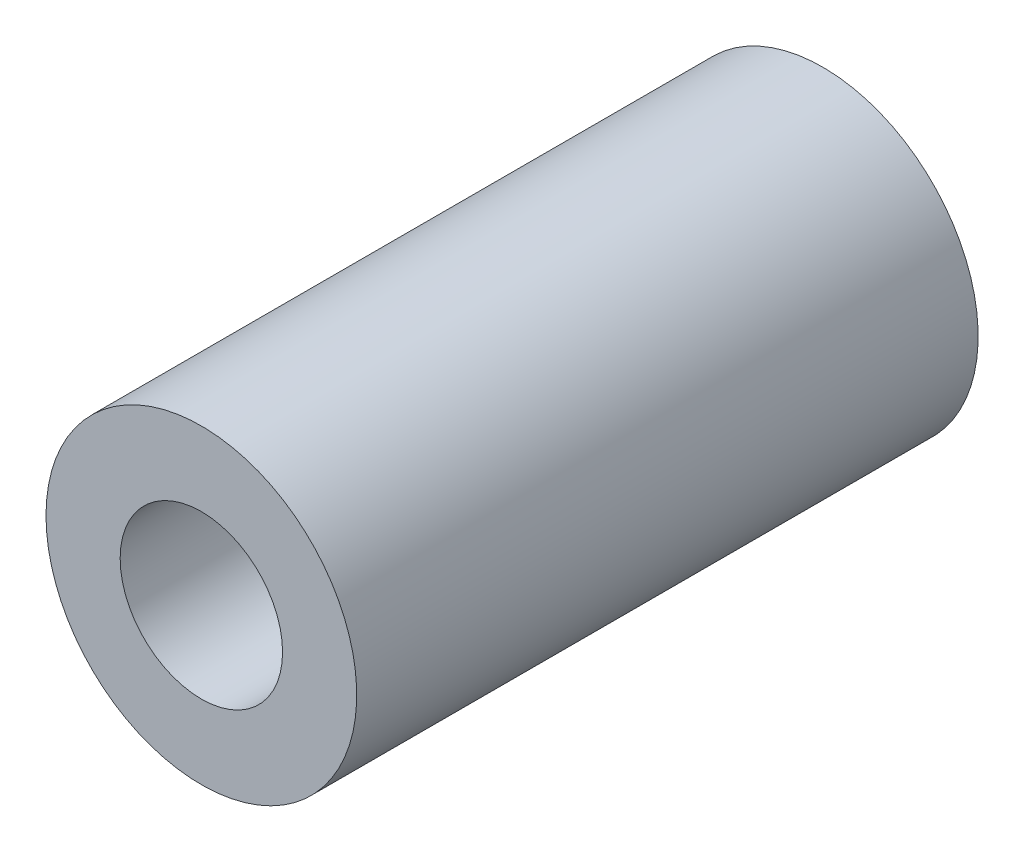
SolidWorks part; units mm, degrees
material "6061-T6 (SS)"
ref_plane "Front Plane" through (0, 0, 0) normal (0, 0, 1) x (1, 0, 0)
ref_plane "Top Plane" through (0, 0, 0) normal (0, 1, 0) x (1, 0, 0)
ref_plane "Right Plane" through (0, 0, 0) normal (1, 0, 0) x (0, 0, -1)
sketch "Sketch1" plane through (0, 0, 0) normal (0, 0, 1) x (1, 0, 0)
  circle A0 centre (0, 0) radius 4.7625
  circle A1 centre (0, 0) radius 2.4892
  dimension "D1" = 9.525
  dimension "D2" = 4.9784
extrude "Boss-Extrude1" add sketch "Sketch1" along normal blind 19.05 contours A0 A1 region at (-4.6278, 0, 0)
